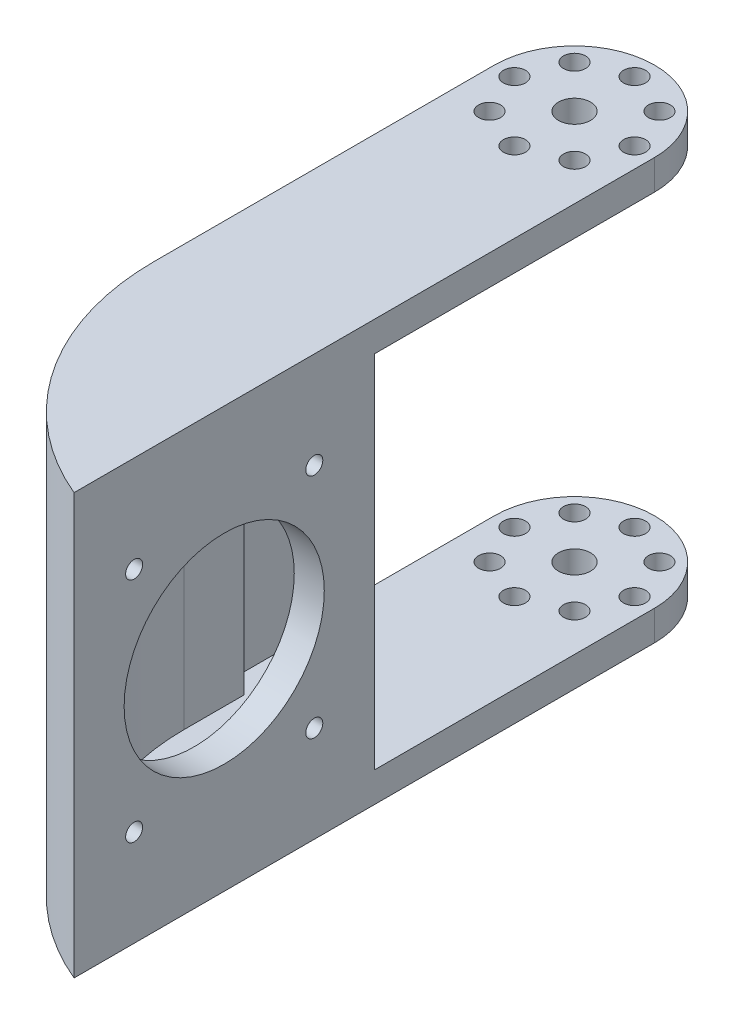
SolidWorks part; units mm, degrees
material "ABS"
ref_plane "正面" through (0, 0, 0) normal (0, 0, 1) x (1, 0, 0)
ref_plane "平面" through (0, 0, 0) normal (0, 1, 0) x (1, 0, 0)
ref_plane "右側面" through (0, 0, 0) normal (1, 0, 0) x (0, 0, -1)
sketch "ｽｹｯﾁ1" plane through (0, 0, 0) normal (0, 1, 0) x (1, 0, 0)
  line L0 (-8, 45) -> (-8, -13)
  line L7 (-8, -13) -> (8, -13)
  line L8 (8, -13) -> (8, 45)
  arc A4 (8, 45) -> (-8, 45) centre (0, 45) ccw
  circle A5 centre (0, 45) radius 6 construction
  circle A6 centre (0, 51) radius 1.1
  circle A7 centre (4.2426, 49.2426) radius 1.1
  circle A8 centre (6, 45) radius 1.1
  circle A9 centre (4.2426, 40.7574) radius 1.1
  circle A10 centre (0, 39) radius 1.1
  circle A11 centre (-4.2426, 40.7574) radius 1.1
  circle A12 centre (-6, 45) radius 1.1
  circle A13 centre (-4.2426, 49.2426) radius 1.1
  circle A14 centre (0, 45) radius 1.6
  point P0 (0, 0)
  point P35 (0, 45)
  dimension "D9" = 45
  dimension "D10" = 12
  dimension "D11" = 2.2
  dimension "D13" = 3.2
  dimension "D6" = 8
  dimension "D7" = 8
  dimension "D8" = 13
  dimension "D12" = 8
extrude "ﾎﾞｽ - 押し出し1" add sketch "ｽｹｯﾁ1" along normal blind 3
ref_plane "平面1" through (0, -36, 0) normal (0, 1, 0) x (1, 0, 0)
sketch "ｽｹｯﾁ2" plane through (0, -36, 0) normal (0, 1, 0) x (1, 0, 0)
  line L3 (8, -13) -> (8, 45)
  line L4 (-8, -13) -> (8, -13)
  line L5 (-8, 45) -> (-8, -13)
  line L6 (8, -13) -> (8, 45)
  line L7 (-8, -13) -> (8, -13)
  line L8 (-8, 45) -> (-8, -13)
  circle A0 centre (0, 45) radius 1.6
  arc A1 (8, 45) -> (-8, 45) centre (0, 45) ccw
  arc A2 (8, 45) -> (-8, 45) centre (0, 45) ccw
  circle A3 centre (0, 45) radius 6 construction
  circle A4 centre (0, 51) radius 1.1
  circle A5 centre (4.2426, 49.2426) radius 1.1
  circle A6 centre (6, 45) radius 1.1
  circle A7 centre (4.2426, 40.7574) radius 1.1
  circle A8 centre (0, 39) radius 1.1
  circle A9 centre (-4.2426, 40.7574) radius 1.1
  circle A10 centre (-6, 45) radius 1.1
  circle A11 centre (-4.2426, 49.2426) radius 1.1
  point P25 (0, 45)
  dimension "D2" = 3.2
  dimension "D3" = 12
  dimension "D4" = 2.2
  dimension "D1" = 0
  dimension "D5" = 8
extrude "ﾎﾞｽ - 押し出し2" add sketch "ｽｹｯﾁ2" against normal blind 3 separate body
sketch "ｽｹｯﾁ3" plane through (0, 0, 13) normal (0, 0, 1) x (1, 0, 0)
  line L1 (-8, -36) -> (8, -36)
  line L2 (-8, -36) -> (-8, 0)
  line L3 (-8, 0) -> (8, 0)
  line L4 (8, -36) -> (8, 0)
extrude "ﾎﾞｽ - 押し出し3" add sketch "ｽｹｯﾁ3" against normal blind 30
fillet "ﾌｨﾚｯﾄ1" radius 26 1 edges at (-8, -18, 13)
sketch "ｽｹｯﾁ5" plane through (-8, 0, 0) normal (-1, 0, 0) x (0, 0, 1)
  line L1 (-17, 0) -> (-31, 0)
  line L2 (-17, 0) -> (-17, -36)
  line L3 (-17, -36) -> (-31, -36)
  line L4 (-31, 0) -> (-31, -36)
  line L5 (-45, -36) -> (-17, -36) construction
  dimension "D1" = 14
extrude "ﾎﾞｽ - 押し出し4" add sketch "ｽｹｯﾁ5" against normal blind 1
sketch "ｽｹｯﾁ7" plane through (0, 0, 0) normal (0, -1, 0) x (1, 0, 0)
  line L0 (5, 7.9737) -> (5, -17)
  line L1 (8, -17) -> (-7, -17) construction
  line L2 (5, -17) -> (-5, -17)
  line L3 (-5, -17) -> (-5, -11)
  line L4 (8, -17) -> (8, -45) construction
  arc A0 (9.1538, 10.2308) -> (-5, -11) centre (18, -11) ccw construction
  arc A2 (8, 13) -> (-8, -11) centre (18, -11) ccw
  arc A3 (8, 13) -> (-8, -11) centre (18, -11) ccw construction
  arc A4 (5, 7.9737) -> (-5, -11) centre (18, -11) ccw
  dimension "D2" = 3
  dimension "D1" = 3
extrude "ｶｯﾄ - 押し出し2" cut sketch "ｽｹｯﾁ7" along normal up to surface (36 mm away) up to face at (-2.3333, -36, -32.3333)
sketch "ｽｹｯﾁ6" plane through (8, 0, 0) normal (1, 0, 0) x (0, 0, -1)
  line L0 (2, 3) -> (2, -39) construction
  line L1 (-13, 3) -> (45, 3) construction
  line L2 (-13, 3) -> (-13, -39) construction
  line L3 (-13, -39) -> (45, -39) construction
  circle A0 centre (2, -18) radius 15 construction
  circle A1 centre (2, -18) radius 20 construction
  circle A2 centre (2, -18) radius 14.5 construction
  circle A3 centre (11, -6.6312) radius 0.85
  circle A4 centre (-7, -6.6312) radius 0.85
  circle A5 centre (-7, -29.3688) radius 0.85
  circle A6 centre (11, -29.3688) radius 0.85
  circle A7 centre (2, -18) radius 10
  dimension "D1" = 30
  dimension "D2" = 40
  dimension "D4" = 29
  dimension "D5" = 1.7
  dimension "D7" = 20
  dimension "D3" = 15
  dimension "D6" = 9
extrude "ｶｯﾄ - 押し出し1" cut sketch "ｽｹｯﾁ6" against normal blind 5
